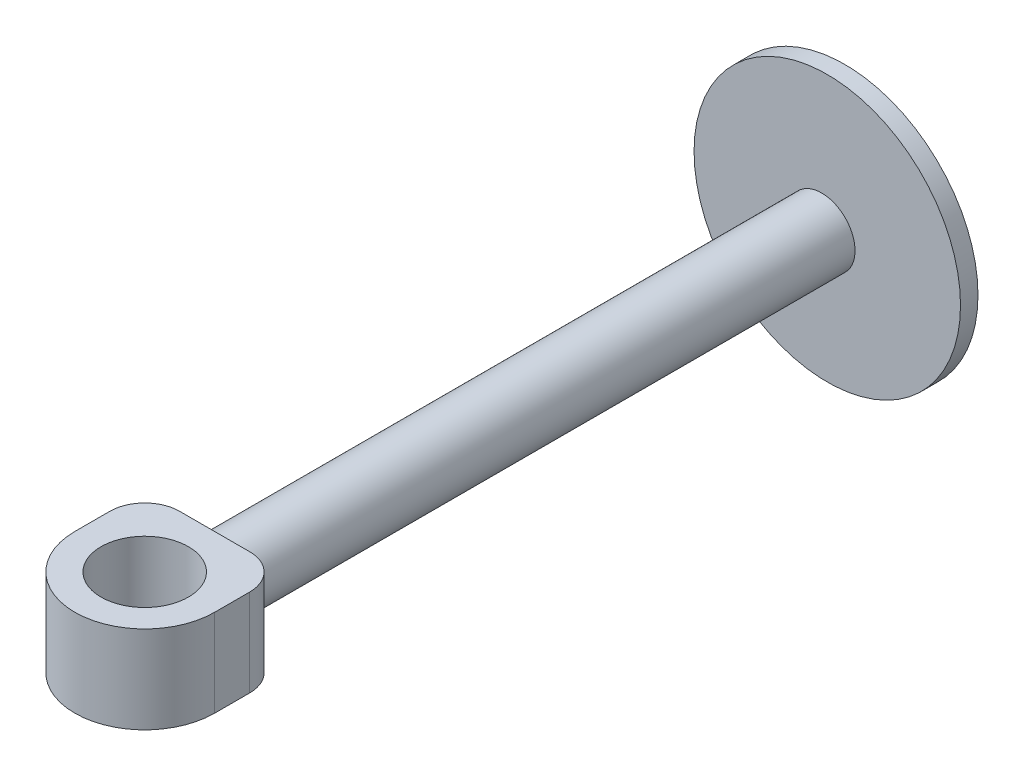
SolidWorks part; units mm, degrees
ref_plane "Płaszczyzna przednia" through (0, 0, 0) normal (0, 0, 1) x (1, 0, 0)
ref_plane "Płaszczyzna górna" through (0, 0, 0) normal (0, 1, 0) x (1, 0, 0)
ref_plane "Płaszczyzna prawa" through (0, 0, 0) normal (1, 0, 0) x (0, 0, -1)
ref_plane "Płaszczyzna1" through (0, 0, 34.7218) normal (0, 0, -1) x (-1, 0, 0)
sketch "Szkic2" plane through (0, 0, 34.7218) normal (0, 0, -1) x (-1, 0, 0)
  line L0 (6.264, -7.1755) -> (-6.264, -7.1755)
  line L1 (-6.264, 7.1755) -> (6.264, 7.1755)
  arc A0 (6.264, 7.1755) -> (6.264, -7.1755) centre (0, 0) cw
  arc A1 (-6.264, -7.1755) -> (-6.264, 7.1755) centre (0, 0) cw
extrude "Dodanie-wyciągnięcie2" add sketch "Szkic2" along normal blind 12.7
sketch "Szkic3" plane through (0, 0, 22.0218) normal (0, 0, -1) x (-1, 0, 0)
  circle A0 centre (0, 0) radius 9.525
extrude "Dodanie-wyciągnięcie3" add sketch "Szkic3" along normal blind 173.6109
ref_plane "Płaszczyzna2" through (0, 0, -153.1766) normal (0, 0, 1) x (1, 0, 0)
sketch "Szkic4" plane through (0, 0, -153.1766) normal (0, 0, 1) x (1, 0, 0)
  circle A0 centre (0, 0) radius 38.1
extrude "Dodanie-wyciągnięcie4" add sketch "Szkic4" against normal blind 5
sketch "Szkic5" plane through (0, 0, 22.0218) normal (0, 0, 1) x (1, 0, 0)
  line L1 (-20, -12.5) -> (20, -12.5)
  line L2 (-20, -12.5) -> (-20, 12.5)
  line L3 (-20, 12.5) -> (20, 12.5)
  line L4 (20, -12.5) -> (20, 12.5)
  line L5 (-20, -12.5) -> (20, 12.5) construction
  line L6 (-20, 12.5) -> (20, -12.5) construction
  point P0 (0, 0)
  dimension "D1" = 25
  dimension "D2" = 40
extrude "Dodanie-wyciągnięcie5" add sketch "Szkic5" along normal blind 40
fillet "Zaokrąglenie1" 2 edges at (-20, 0, 62.0218) (20, 0, 62.0218) type full round first side face at (-20, 0, 42.0218) second side face at (20, 0, 42.0218) middle face at (0, 0, 62.0218)
fillet "Zaokrąglenie2" radius 10 2 edges at (20, 0, 22.0218) (-20, 0, 22.0218)
sketch "Szkic6" plane through (0, 12.5, 0) normal (0, 1, 0) x (1, 0, 0)
  circle A0 centre (0, -42.0218) radius 12.5
  dimension "D1" = 25
extrude "Wytnij-wyciągnięcie1" cut sketch "Szkic6" against normal up to next (25 mm away)
